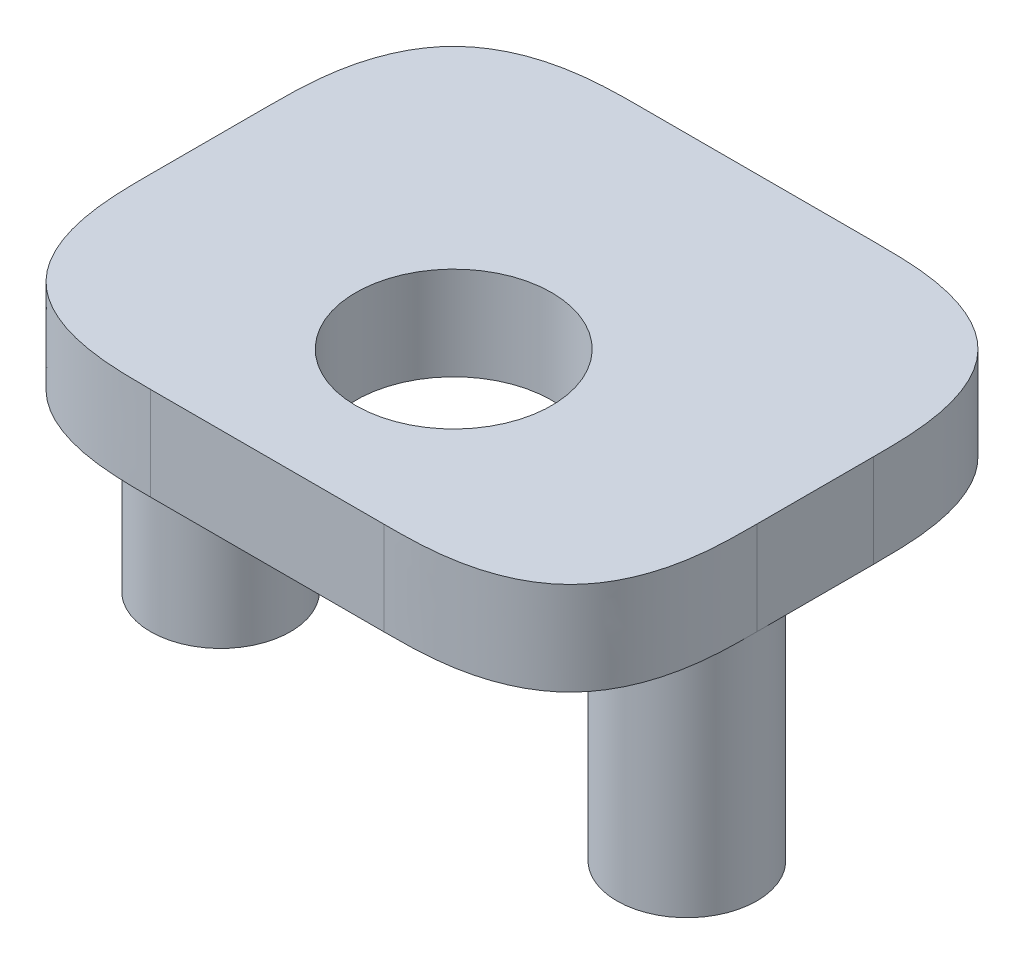
SolidWorks part; units mm, degrees
ref_plane "前视基准面" through (0, 0, 0) normal (0, 0, 1) x (1, 0, 0)
ref_plane "上视基准面" through (0, 0, 0) normal (0, 1, 0) x (1, 0, 0)
ref_plane "右视基准面" through (0, 0, 0) normal (1, 0, 0) x (0, 0, -1)
other "Configuration Table"
sketch "草图1" plane through (0, 0, 0) normal (0, 1, 0) x (1, 0, 0)
  line L0 (0, 0) -> (82.2418, 0) construction
  line L1 (0, 0) -> (0, 65.7222) construction
  circle A0 centre (0, 0) radius 2.1
  circle A1 centre (5, 0) radius 1.5
  circle A3 centre (-5, 0) radius 1.5
  circle A4 centre (0, 5) radius 1.5
  circle A5 centre (0, -5) radius 1.5 [skipped]
  circle A6 centre (5, 0) radius 0.95
  circle A8 centre (-5, 0) radius 0.95
  circle A9 centre (0, 5) radius 0.95
  circle A10 centre (0, -5) radius 0.95 [skipped]
  dimension "D1" = 4.2
  dimension "D2" = 3
  dimension "D5" = 1.9
  dimension "D3" = 5
  dimension "D4" = 4
  dimension "D6" = 4
extrude "凸台-拉伸1" add sketch "草图1" along normal blind 5 contours A3 | A4 | A1 | A3 | A4 | A1 region at (3.5424, 0, 0) region at (-6.4576, 0, 0) region at (-1.4576, 0, -5)
sketch "草图2" plane through (0, 5, 0) normal (0, 1, 0) x (1, 0, 0)
  line L1 (-6.5, -4) -> (6.5, -4)
  line L2 (-6.5, -4) -> (-6.5, 6.5)
  line L3 (-6.5, 6.5) -> (6.5, 6.5)
  line L4 (6.5, -4) -> (6.5, 6.5)
  circle A0 centre (-5, 0) radius 1.5 construction
  circle A1 centre (0, 5) radius 1.5 construction
  circle A2 centre (5, 0) radius 1.5 construction
  dimension "D1" = 4
extrude "凸台-拉伸6" add sketch "草图2" along normal blind 2
extrude "切除-拉伸2" cut sketch "草图1<6>" along normal up to surface (7 mm away) contours A0 region at (0, 0, 0) up to face at (0, 7, -1.25)
sketch "草图1<6>" plane through (0, 0, 0) normal (0, 1, 0) x (1, 0, 0) same geometry as "草图1"
fillet "圆角1" radius 4 4 edges at (6.5, 6, -6.5) (-6.5, 6, -6.5) (6.5, 6, 4) (-6.5, 6, 4) curvature continuous yes
extrude "切除-拉伸3" cut sketch "草图1<7>" along normal blind 6 contours A6 | A9 | A8 region at (5, 0, 0) region at (-5, 0, 0) region at (0, 0, -5)
sketch "草图1<7>" plane through (0, 0, 0) normal (0, 1, 0) x (1, 0, 0) same geometry as "草图1"
